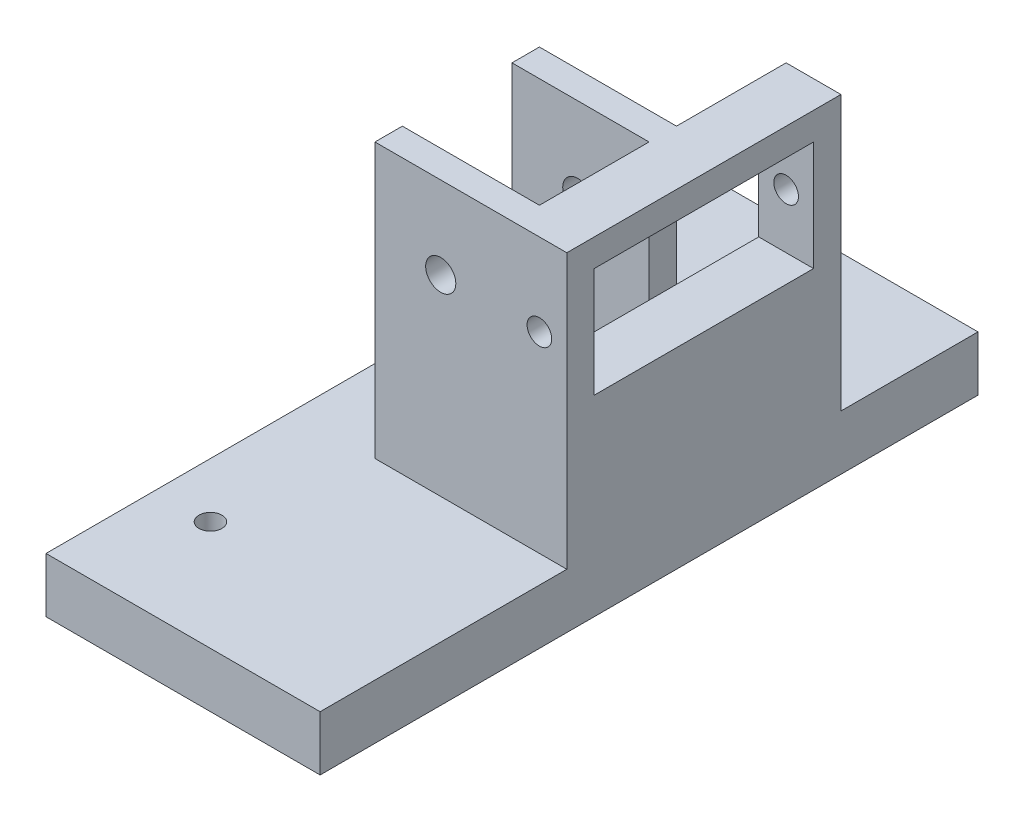
SolidWorks part; units mm, degrees
ref_plane "Front Plane" through (0, 0, 0) normal (0, 0, 1) x (1, 0, 0)
ref_plane "Top Plane" through (0, 0, 0) normal (0, 1, 0) x (1, 0, 0)
ref_plane "Right Plane" through (0, 0, 0) normal (1, 0, 0) x (0, 0, -1)
sketch "Sketch4" plane through (0, 0, 0) normal (0, 1, 0) x (1, 0, 0)
  line L1 (0, 0) -> (40, 0)
  line L2 (0, 0) -> (0, 80)
  line L3 (0, 80) -> (40, 80)
  line L4 (40, 0) -> (40, 80)
  dimension "D1" = 80
  dimension "D2" = 40
extrude "Boss-Extrude4" add sketch "Sketch4" along normal blind 5
sketch "Sketch5" plane through (0, 5, 0) normal (0, 1, 0) x (1, 0, 0)
  line L0 (40, 40) -> (30, 40)
  line L1 (30, 30) -> (30, 50) construction
  line L2 (40, 50) -> (30, 50)
  line L3 (30, 50) -> (30, 55)
  line L4 (0, 80) -> (0, 0)
  line L5 (0, 0) -> (40, 0)
  line L6 (40, 0) -> (40, 80)
  line L7 (40, 80) -> (0, 80)
  line L8 (0, 80) -> (0, 0)
  line L9 (0, 0) -> (40, 0)
  line L10 (40, 0) -> (40, 80)
  line L11 (40, 80) -> (0, 80)
  line L12 (30, 55) -> (40, 55)
  line L13 (40, 55) -> (40, 50)
  line L14 (40, 30) -> (30, 30)
  line L15 (30, 30) -> (30, 25)
  line L16 (30, 25) -> (40, 25)
  line L17 (40, 25) -> (40, 30)
  point P9 (30, 40)
  line M11 (40, 0) -> (40, 80)
  dimension "D2" = 10
  dimension "D3" = 10
  dimension "D4" = 5
  dimension "D5" = 5
  dimension "D1" = 0
extrude "Boss-Extrude6" add sketch "Sketch5" along normal blind 50 contours L12 L3 L2 M11 | L15 L16 L10 L14 region at (35, 5, -52.5) region at (35, 5, -27.5)
sketch "Sketch7" plane through (0, 0, -50) normal (0, 0, 1) x (1, 0, 0)
  line L1 (30, 5) -> (40, 5)
  line L2 (30, 5) -> (30, 30)
  line L3 (30, 30) -> (40, 30)
  line L4 (40, 5) -> (40, 30)
  line L5 (40, 55) -> (40, 5) construction
  line L7 (30, 55) -> (40, 55)
  line L8 (30, 55) -> (30, 50)
  line L9 (30, 50) -> (40, 50)
  line L10 (40, 55) -> (40, 50)
  dimension "D1" = 25
  dimension "D2" = 10
  dimension "D3" = 5
extrude "Boss-Extrude7" add sketch "Sketch7" along normal up to surface (20 mm away) contours L8 L7 L10 L9 | L2 L1 L4 L3 up to face at (35, 30, -30)
sketch "Sketch9" plane through (0, 0, 0) normal (-1, 0, 0) x (0, 0, 1)
  line L4 (-80, 0) -> (0, 0)
  line L5 (0, 0) -> (0, 5)
  line L6 (0, 5) -> (-80, 5)
  line L7 (-80, 5) -> (-80, 0)
  line L8 (-80, 0) -> (0, 0)
  line L9 (0, 0) -> (0, 5)
  line L10 (0, 5) -> (-80, 5)
  line L12 (-80, 5) -> (-80, 0)
  dimension "D1" = 0
extrude "Boss-Extrude9" add sketch "Sketch9" along normal blind 10
sketch "Sketch10" plane through (0, 0, 0) normal (0, 0, 1) x (1, 0, 0)
  line L4 (-10, 0) -> (40, 0)
  line L5 (40, 0) -> (40, 5)
  line L6 (40, 5) -> (-10, 5)
  line L7 (-10, 5) -> (-10, 0)
  line L8 (-10, 0) -> (40, 0)
  line L9 (40, 0) -> (40, 5)
  line L10 (40, 5) -> (-10, 5)
  line L11 (-10, 5) -> (-10, 0)
  dimension "D1" = 0
extrude "Boss-Extrude10" add sketch "Sketch10" along normal blind 20
sketch "Sketch11" plane through (0, 0, -50) normal (0, 0, 1) x (1, 0, 0)
  line L0 (30, 40) -> (35, 40)
  line L4 (30, 30) -> (40, 30)
  line L5 (40, 30) -> (40, 50)
  line L6 (40, 50) -> (30, 50)
  line L7 (30, 50) -> (30, 30)
  line L8 (30, 30) -> (40, 30)
  line L9 (40, 30) -> (40, 50)
  line L10 (40, 50) -> (30, 50)
  line L11 (30, 50) -> (30, 30)
  circle A0 centre (35, 40) radius 2.25
  dimension "D3" = 4.5
  dimension "D2" = 5
  dimension "D1" = 0
extrude "Cut-Extrude1" cut sketch "Sketch11" against normal mid plane 50 contours A0 region at (35, 42.1864, -50)
sketch "Sketch12" plane through (0, 0, -25) normal (0, 0, 1) x (1, 0, 0)
  circle A0 centre (35, 40) radius 2.25 construction
  circle A1 centre (35, 40) radius 2.25
  circle A2 centre (35, 40) radius 4
  dimension "D1" = 8
extrude "Cut-Extrude2" cut sketch "Sketch12" against normal blind 2
sketch "Sketch15" plane through (30, 0, 0) normal (-1, 0, 0) x (0, 0, 1)
  line L1 (-55, 55) -> (-50, 55)
  line L2 (-55, 55) -> (-55, 5)
  line L3 (-55, 5) -> (-50, 5)
  line L4 (-50, 55) -> (-50, 5)
  line L5 (-25, 55) -> (-30, 55)
  line L6 (-25, 55) -> (-25, 5)
  line L7 (-25, 5) -> (-30, 5)
  line L8 (-30, 55) -> (-30, 5)
  dimension "D1" = 50
  dimension "D2" = 5
  dimension "D3" = 50
  dimension "D4" = 5
extrude "Boss-Extrude11" add sketch "Sketch15" along normal blind 20
sketch "Sketch16" plane through (0, 0, -25) normal (0, 0, 1) x (1, 0, 0)
  line L0 (35, 40) -> (17, 40)
  circle A0 centre (35, 40) radius 4 construction
  circle A1 centre (35, 40) radius 4
  circle A2 centre (17, 40) radius 2.75
  dimension "D2" = 5.5
  dimension "D1" = 18
extrude "Cut-Extrude4" cut sketch "Sketch16" against normal up to surface (30 mm away) contours A2 region at (14.3278, 40, -25) up to face at (32.75, 40, -55)
sketch "Sketch19" plane through (10, 0, 0) normal (-1, 0, 0) x (0, 0, 1)
  line L4 (-55, 55) -> (-55, 5)
  line L5 (-55, 5) -> (-50, 5)
  line L6 (-50, 5) -> (-50, 55)
  line L7 (-50, 55) -> (-55, 55)
  line L8 (-55, 55) -> (-55, 5)
  line L10 (-50, 5) -> (-50, 55)
  line L11 (-50, 55) -> (-55, 55)
  line L12 (-25, 5) -> (-25, 55)
  line L13 (-25, 55) -> (-30, 55)
  line L14 (-30, 55) -> (-30, 5)
  line L15 (-30, 5) -> (-25, 5)
  line L16 (-25, 5) -> (-25, 55)
  line L17 (-25, 55) -> (-30, 55)
  line L18 (-30, 55) -> (-30, 5)
  line L20 (-55, 5) -> (-50, 5)
  line L21 (-30, 5) -> (-25, 5)
  dimension "D1" = 0
  dimension "D2" = 0
extrude "Boss-Extrude12" add sketch "Sketch19" along normal blind 5
sketch "Sketch21" plane through (0, 0, 0) normal (0, -1, 0) x (1, 0, 0)
  line L4 (40, -80) -> (40, 20)
  line L5 (40, 20) -> (-10, 20)
  line L6 (-10, 20) -> (-10, -80)
  line L7 (-10, -80) -> (40, -80)
  line L8 (40, -80) -> (40, 20)
  line L9 (40, 20) -> (-10, 20)
  line L10 (-10, 20) -> (-10, -80)
  line L11 (-10, -80) -> (40, -80)
  dimension "D1" = 0
extrude "Boss-Extrude14" add sketch "Sketch21" along normal blind 5
sketch "Sketch22" plane through (0, 0, -80) normal (0, 0, -1) x (-1, 0, 0)
  line L4 (-40, 5) -> (-40, -5)
  line L5 (-40, -5) -> (10, -5)
  line L6 (10, -5) -> (10, 5)
  line L7 (10, 5) -> (-40, 5)
  line L8 (-40, 5) -> (-40, -5)
  line L9 (-40, -5) -> (10, -5)
  line L10 (10, -5) -> (10, 5)
  line L11 (10, 5) -> (-40, 5)
  dimension "D1" = 0
extrude "Boss-Extrude15" add sketch "Sketch22" along normal blind 20
sketch "Sketch24" plane through (0, 55, 0) normal (0, 1, 0) x (1, 0, 0)
  line L1 (5, 55) -> (40, 55)
  line L2 (5, 55) -> (5, 50)
  line L3 (5, 50) -> (40, 50)
  line L4 (40, 55) -> (40, 50)
  line L5 (40, 25) -> (40, 55) construction
  dimension "D1" = 35
  dimension "D2" = 5
extrude "Cut-Extrude5" cut sketch "Sketch24" against normal blind 50
sketch "Sketch25" plane through (0, 0, -50) normal (0, 0, -1) x (-1, 0, 0)
  line L4 (-30, 5) -> (-30, 30)
  line L5 (-30, 30) -> (-40, 30)
  line L6 (-40, 30) -> (-40, 5)
  line L7 (-40, 5) -> (-30, 5)
  line L8 (-30, 5) -> (-30, 30)
  line L9 (-30, 30) -> (-40, 30)
  line L10 (-40, 30) -> (-40, 5)
  line L11 (-40, 5) -> (-30, 5)
  line L12 (-30, 50) -> (-30, 55)
  line L13 (-30, 55) -> (-40, 55)
  line L14 (-40, 55) -> (-40, 50)
  line L15 (-40, 50) -> (-30, 50)
  line L16 (-30, 50) -> (-30, 55)
  line L17 (-30, 55) -> (-40, 55)
  line L18 (-40, 55) -> (-40, 50)
  line L19 (-40, 50) -> (-30, 50)
  dimension "D1" = 0
  dimension "D2" = 0
extrude "Boss-Extrude16" add sketch "Sketch25" along normal blind 25
sketch "Sketch26" plane through (0, 30, 0) normal (0, 1, 0) x (1, 0, 0)
  line L1 (40, 75) -> (30, 75)
  line L2 (40, 75) -> (40, 70)
  line L3 (40, 70) -> (30, 70)
  line L4 (30, 75) -> (30, 70)
  line L5 (30, 30) -> (30, 75) construction
  dimension "D1" = 5
  dimension "D2" = 10
extrude "Boss-Extrude17" add sketch "Sketch26" along normal blind 20
sketch "Sketch27" plane through (0, 0, -27) normal (0, 0, 1) x (1, 0, 0)
  circle A0 centre (35, 40) radius 2.25 construction
  circle A1 centre (35, 40) radius 4
  circle A2 centre (35, 40) radius 4
  circle A3 centre (35, 40) radius 2.25
  dimension "D1" = 0
extrude "Boss-Extrude18" add sketch "Sketch27" along normal up to surface (2 mm away) up to face at (19.75, 40, -25)
sketch "Sketch28" plane through (0, 0, -25) normal (0, 0, 1) x (1, 0, 0)
  circle A0 centre (35, 40) radius 2.25 construction
  circle A1 centre (35, 40) radius 2.25
extrude "Cut-Extrude6" cut sketch "Sketch28" against normal blind 50
sketch "Sketch29" plane through (0, 5, 0) normal (0, 1, 0) x (1, 0, 0)
  line L0 (5, 30) -> (5, 50) construction
  line L2 (5, 50) -> (30, 50)
  line L3 (5, 50) -> (5, 55)
  line L4 (5, 55) -> (30, 55)
  line L5 (30, 50) -> (30, 55)
  line L6 (30, 30) -> (30, 75) construction
  dimension "D1" = 20
  dimension "D2" = 5
  dimension "D3" = 25
extrude "Boss-Extrude19" add sketch "Sketch29" along normal up to surface (50 mm away) contours L3 L2 L5 L4 up to face at (25, 55, -43.3333)
sketch "Sketch31" plane through (0, 0, -25) normal (0, 0, 1) x (1, 0, 0)
  circle A0 centre (17, 40) radius 2.75 construction
  circle A1 centre (17, 40) radius 2.75
extrude "Cut-Extrude7" cut sketch "Sketch31" against normal blind 30
sketch "Sketch32" plane through (0, -5, 0) normal (0, -1, 0) x (1, 0, 0)
  line L0 (-10, 20) -> (0, 20) construction
  line L1 (40, 20) -> (-10, 20) construction
  line L2 (0, 20) -> (0, 0) construction
  line L3 (0, 0) -> (0, -80) construction
  circle A0 centre (0, -80) radius 2.1
  circle A1 centre (0, 0) radius 2.1
  dimension "D4" = 4.2
  dimension "D5" = 4.2
  dimension "D1" = 20
  dimension "D2" = 80
  dimension "D3" = 10
extrude "Cut-Extrude8" cut sketch "Sketch32" against normal blind 10 contours A0 | A1
